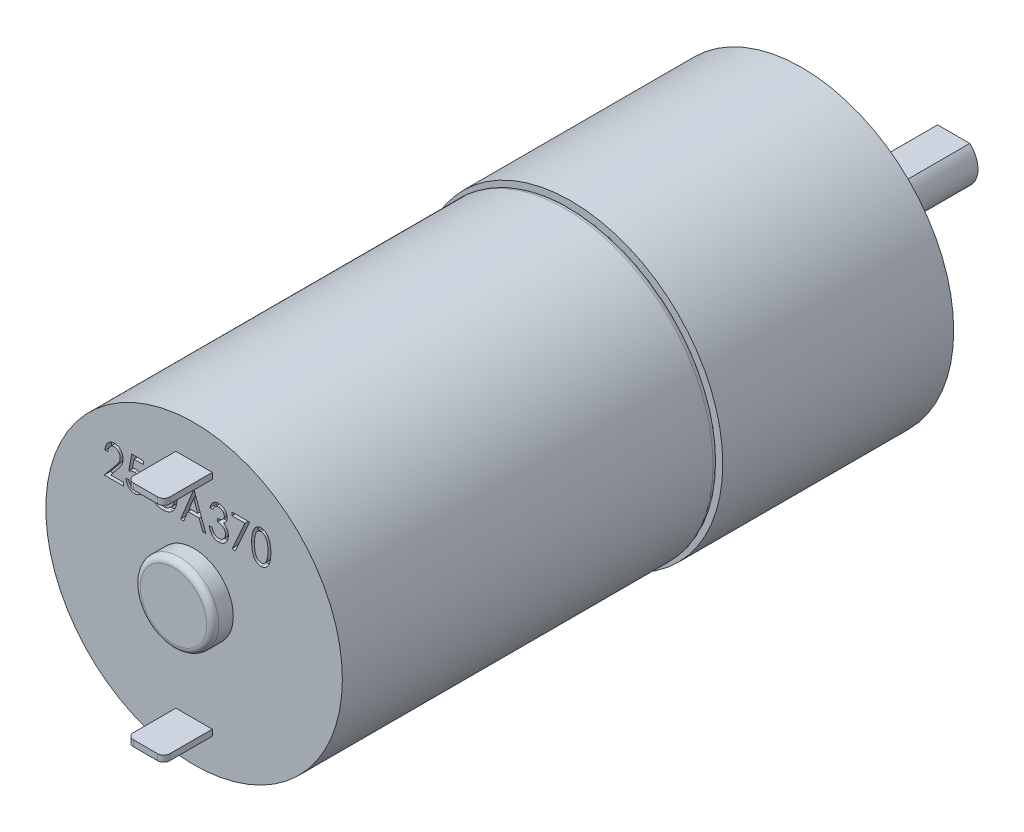
SolidWorks part; units mm, degrees
ref_plane "Front Plane" through (0, 0, 0) normal (0, 0, 1) x (1, 0, 0)
ref_plane "Top Plane" through (0, 0, 0) normal (0, 1, 0) x (1, 0, 0)
ref_plane "Right Plane" through (0, 0, 0) normal (1, 0, 0) x (0, 0, -1)
sketch "Sketch1" plane through (0, 0, 0) normal (0, 0, 1) x (1, 0, 0)
  circle A0 centre (0, 0) radius 12.2
  dimension "D1" = 24.4
extrude "Boss-Extrude1" add sketch "Sketch1" along normal blind 31
fillet "Fillet1" radius 0.5 1 edges at (12.2, 0, 0)
sketch "Sketch2" plane through (0, 0, 0) normal (0, 0, -1) x (-1, 0, 0)
  circle A0 centre (0, 0) radius 12.5
extrude "Boss-Extrude2" add sketch "Sketch2" along normal blind 19
sketch "Sketch4" plane through (0, 0, -19) normal (0, 0, -1) x (-1, 0, 0)
  circle A0 centre (0, 0) radius 3.5
  circle A1 centre (0, 0) radius 2.5
  dimension "D1" = 7
  dimension "D2" = 5
extrude "Boss-Extrude3" add sketch "Sketch4" along normal blind 2 contours A0
sketch "Sketch6" plane through (0, 0, -21) normal (0, 0, -1) x (-1, 0, 0)
  circle A0 centre (0, 0) radius 2
  dimension "D1" = 4
extrude "Boss-Extrude4" add sketch "Sketch6" along normal blind 10.5
sketch "Sketch7" plane through (0, 0, -31.5) normal (0, 0, -1) x (-1, 0, 0)
  line L0 (-1.3229, 1.5) -> (1.3229, 1.5)
  line L1 (0, 0) -> (0, 12.5) construction
  circle A0 centre (0, 0) radius 2 construction
  arc A1 (-1.3229, 1.5) -> (1.3229, 1.5) centre (0, 0) cw
  circle A3 centre (0, 0) radius 12.5 construction
  dimension "D1" = 1.5
extrude "Cut-Extrude1" cut sketch "Sketch7" against normal blind 7
fillet "Fillet2" radius 1 1 edges at (0, 1.5, -24.5)
sketch "Sketch9" plane through (0, 0, 31) normal (0, 0, 1) x (1, 0, 0)
  circle A0 centre (0, 0) radius 3.225
  dimension "D1" = 6.45
extrude "Boss-Extrude5" add sketch "Sketch9" along normal blind 1.7
fillet "Fillet3" radius 0.5 1 edges at (3.225, 0, 32.7)
sketch "Sketch10" plane through (0, 0, 31) normal (0, 0, 1) x (1, 0, 0)
  line L0 (0, 11.2262) -> (0, -11.0261) construction
  line L1 (0, 0) -> (-8.0308, 0) construction
  line L2 (-1.5, 9.4) -> (1.5, 9.4)
  line L3 (-1.5, 9.4) -> (-1.5, 8.9)
  line L4 (-1.5, 8.9) -> (1.5, 8.9)
  line L5 (1.5, 9.4) -> (1.5, 8.9)
  line L6 (1.5, -9.4) -> (1.5, -8.9)
  line L7 (-1.5, -8.9) -> (1.5, -8.9)
  line L8 (-1.5, -9.4) -> (-1.5, -8.9)
  line L9 (-1.5, -9.4) -> (1.5, -9.4)
  point P7 (0, 8.9)
  point P15 (0, 9.4)
  dimension "D1" = 3
  dimension "D2" = 0.5
  dimension "D3" = 8.9
  dimension "D4" = 1.5
extrude "Boss-Extrude6" add sketch "Sketch10" along normal blind 4
fillet "Fillet4" radius 0.5 4 edges at (1.5, -9.15, 35) (-1.5, -9.15, 35) (1.5, 9.15, 35) (-1.5, 9.15, 35)
hole_wizard "M3 螺纹孔的螺纹孔钻头1" positions "Sketch12" profile "Sketch13" hole size "M3" standard "DIN"
sketch "Sketch12" plane through (0, 0, -19) normal (0, 0, -1) x (-1, 0, 0)
  point P0 (0, 8.5)
  point P2 (0, -8.5)
  dimension "D1" = 17
  dimension "D2" = 8.5
sketch "Sketch13" plane through (0, 8.5, -19) normal (1, 0, 0) x (0, 1, 0)
  line L0 (0, 0) -> (0, 4.2511)
  line L1 (0, 4.2511) -> (1.25, 3.5)
  line L2 (1.25, 3.5) -> (1.25, 0)
  line L5 (1.25, 0) -> (0, 0)
  line L10 (0, 4.2511) -> (-1.25, 3.5) construction
  line L11 (0, -6.35) -> (0, 107.95) construction
  dimension "Hole Dia." = 2.5
  dimension "Hole Depth" = 3.5
  dimension "Drill Angle" = 118
fillet "Fillet5" radius 0.25 1 edges at (-3.5, 0, -21)
sketch "Sketch14" plane through (0, 0, 31) normal (0, 0, 1) x (1, 0, 0)
  text T0 "25GA370" font "Century Gothic" height in points 10
extrude "Cut-Extrude2" cut sketch "Sketch14" against normal blind 0.5
